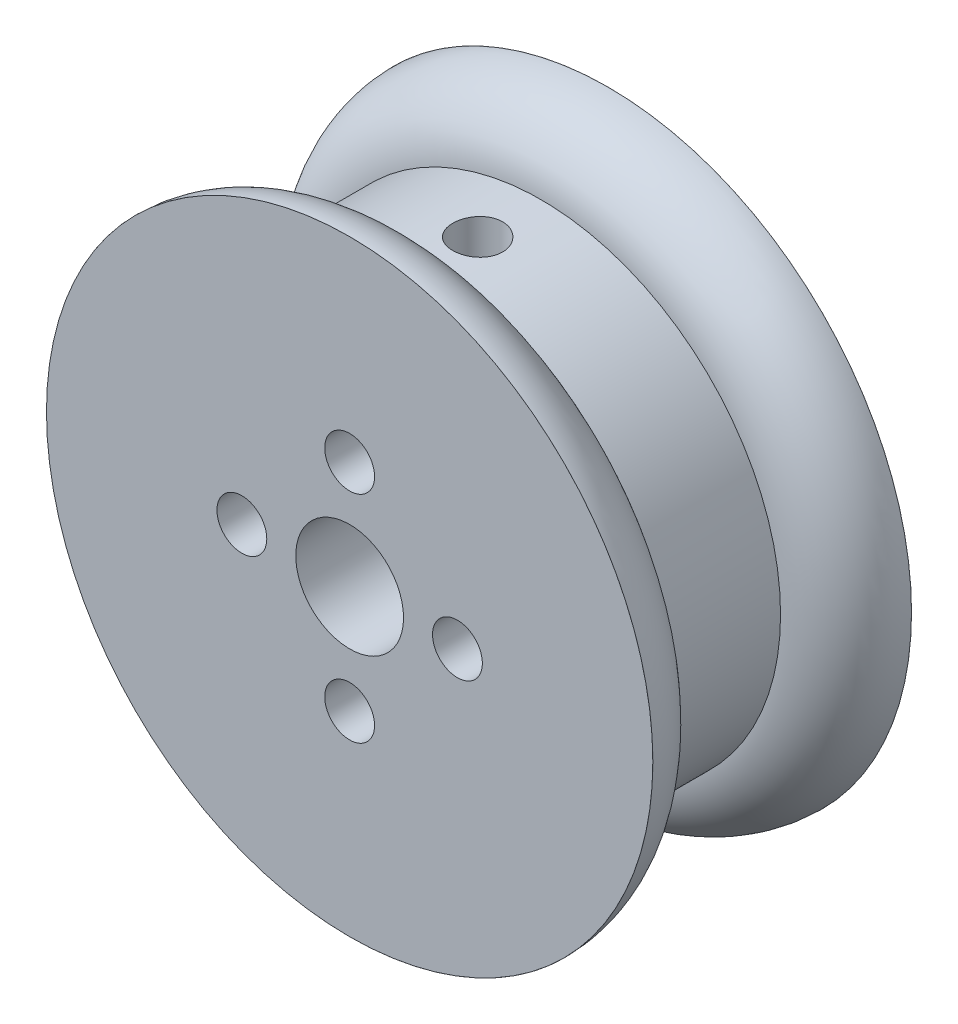
SolidWorks part; units mm, degrees
ref_plane "Front Plane" through (0, 0, 0) normal (0, 0, 1) x (1, 0, 0)
ref_plane "Top Plane" through (0, 0, 0) normal (0, 1, 0) x (1, 0, 0)
ref_plane "Right Plane" through (0, 0, 0) normal (1, 0, 0) x (0, 0, -1)
sketch "Sketch1" plane through (0, 0, 0) normal (0, 0, 1) x (1, 0, 0)
  circle A5 centre (0, 0) radius 22.5
  dimension "D1" = 45
extrude "Boss-Extrude1" add sketch "Sketch1" along normal blind 5
sketch "Sketch2" plane through (0, 0, 0) normal (0, 0, 1) x (1, 0, 0)
  circle A0 centre (0, 0) radius 17.78
  dimension "D1" = 35.56
extrude "Boss-Extrude2" add sketch "Sketch2" against normal blind 9.2
sketch "Sketch5" plane through (0, 0, -9.2) normal (0, 0, -1) x (-1, 0, 0)
  circle A2 centre (0, 0) radius 22.5
  circle A3 centre (0, 0) radius 22.5
  dimension "D1" = 0
extrude "Boss-Extrude4" add sketch "Sketch5" along normal blind 5
sketch "Sketch6" plane through (0, 0, 5) normal (0, 0, 1) x (1, 0, 0)
  line L0 (0, 0) -> (0, 8) construction
  circle A0 centre (0, 0) radius 4
  circle A1 centre (0, 8) radius 1.85
  circle A2 centre (8, 0) radius 1.85
  circle A3 centre (0, -8) radius 1.85
  circle A4 centre (-8, 0) radius 1.85
  point P14 (0, 0)
  dimension "D1" = 8
  dimension "D3" = 3.7
  dimension "D2" = 8
  dimension "D4" = 4
extrude "Cut-Extrude1" cut sketch "Sketch6" against normal through all
fillet "Fillet1" radius 5 2 edges at (22.5, 0, 0) (-22.5, 0, -9.2)
ref_plane "Plane1" through (0, 0, -14.2) normal (0, 0, -1) x (-1, 0, 0)
sketch "Sketch8" plane through (0, 0, 0) normal (0, 1, 0) x (1, 0, 0)
  line L0 (-4, -5) -> (4, -5) construction
  circle A0 centre (0, 4.5) radius 1.85
  dimension "D1" = 3.7
  dimension "D2" = 9.5
extrude "Cut-Extrude2" cut sketch "Sketch8" against normal blind 26 and the other way blind 26
